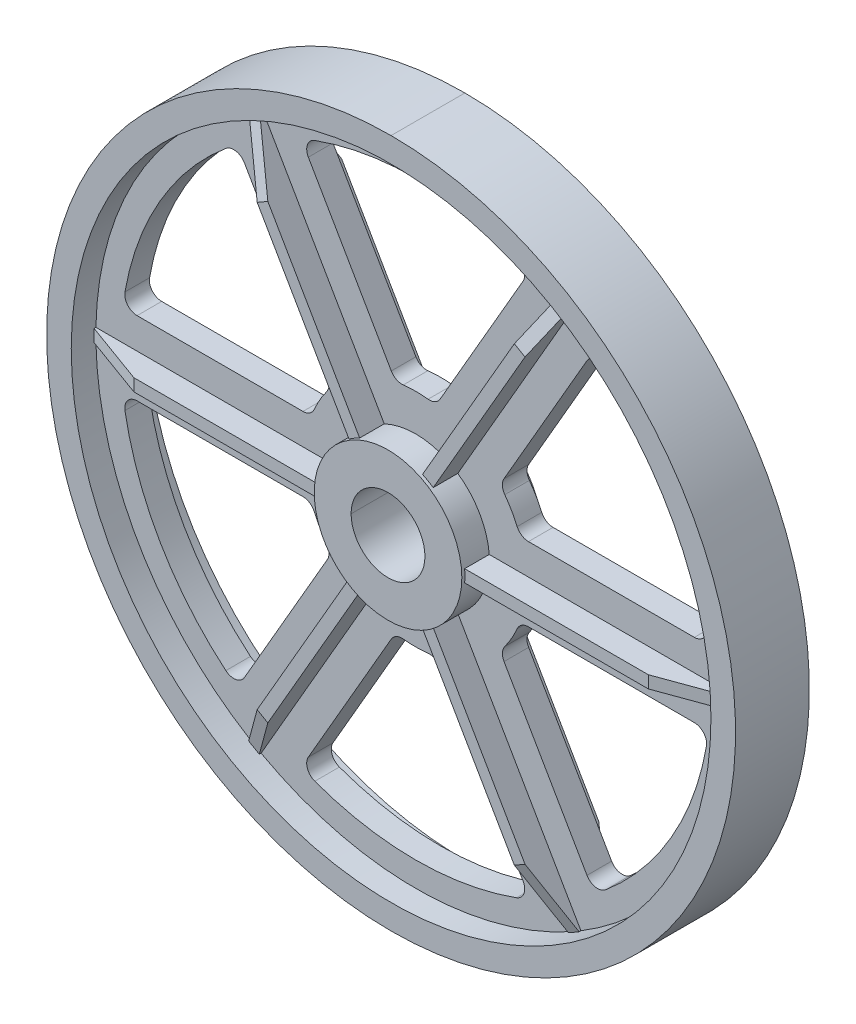
SolidWorks part; units mm, degrees
note: '?' marks a value the reader was unsure of.
extrude "CenterHub" add sketch "Sketch1" along normal mid plane 41.275
sketch "Sketch1" plane through (0, 0, 0) normal (0, 0, 1) x (1, 0, 0)
  circle A0 centre (0, 0) radius 38.1
  dimension "D1" = 76.2
revolve "Rim and Web" add sketch "Sketch2" angle 360 about L0
sketch "Sketch2" plane through (0, 0, 0) normal (1, 0, 0) x (0, 0, -1)
  line L0 (0, 0) -> (51.266, 0) construction
  line L1 (-6.35, 0) -> (6.35, 0)
  line L2 (-6.35, 0) -> (-6.35, 165.1)
  line L3 (-6.35, 165.1) -> (-19.05, 165.1)
  line L4 (6.35, 165.1) -> (6.35, 0)
  line L5 (-19.05, 177.8) -> (19.05, 177.8)
  line L6 (-19.05, 177.8) -> (-19.05, 165.1)
  line L7 (19.05, 165.1) -> (6.35, 165.1)
  line L8 (19.05, 165.1) -> (19.05, 177.8)
  line L9 (0, 0) -> (0, 95.9354) construction
  dimension "D1" = 355.6
  dimension "D2" = 12.7
  dimension "D3" = 38.1
  dimension "D4" = 12.7
ref_plane "Plane1" through (0, 0, 0) normal (0, 0, 1) x (1, 0, 0)
ref_plane "Plane2" through (0, 0, 0) normal (0, 1, 0) x (1, 0, 0)
ref_plane "Plane3" through (0, 0, 0) normal (1, 0, 0) x (0, 0, -1)
other "Configuration Table"
sketch "Sketch3" plane through (0, 0, 0) normal (0, 1, 0) x (1, 0, 0)
  line L0 (0, 0) -> (193.8767, 0) construction
  line L1 (0, -19.05) -> (132.747, -19.05)
  line L2 (132.747, -19.05) -> (167.64, -6.35)
  line L3 (165.1, -6.35) -> (-165.1, -6.35) construction
  line L4 (167.64, -6.35) -> (167.64, 6.35)
  line L5 (132.747, 19.05) -> (167.64, 6.35)
  line L6 (0, 19.05) -> (132.747, 19.05)
  line L7 (0, -19.05) -> (0, 19.05)
  line L8 (165.1, -19.05) -> (-165.1, -19.05) construction
  line L9 (165.1, -19.05) -> (165.1, -6.35) construction
  point P10 (167.64, 0)
  dimension "D1" = 20
  dimension "D2" = 2.54
extrude "Rib" add sketch "Sketch3" along normal mid plane 6.35
sketch "Sketch4" plane through (0, 0, 0) normal (0, 0, 1) x (1, 0, 0)
  line L0 (0, 0) -> (202.3803, 0) construction
  line L1 (0, 0) -> (96.4485, -167.0538) construction
  line L2 (92.1001, -121.4221) -> (43.4386, -37.1378)
  line L3 (151.2047, -19.05) -> (53.8815, -19.05)
  circle A1 centre (0, 0) radius 57.15
  arc A3 (43.4386, -37.1378) -> (53.8815, -19.05) centre (0, 0) ccw
  circle A4 centre (0, 0) radius 152.4
  arc A5 (92.1001, -121.4221) -> (151.2047, -19.05) centre (0, 0) ccw
  dimension "D1" = 19.05
  dimension "D2" = 19.05
  dimension "D5" = 60
  dimension "D3" = 19.05
  dimension "D4" = 12.7
extrude "Lightening hole" cut sketch "Sketch4" against normal through all and the other way through all
fillet "Fillet1" radius 6.35 4 edges at (151.2047, -19.05, 0) (92.1001, -121.4221, 0) (43.4386, -37.1378, 0) (53.8815, -19.05, 0)
pattern_circular "CirPattern1" count 6 every 60 about axis through (0, 0, 0) along (0, 0, 1) of "Lightening hole", "Fillet1", "Rib"
sketch "Sketch5" plane through (0, 0, 0) normal (0, 0, 1) x (1, 0, 0)
  circle A0 centre (0, 0) radius 19.05
  dimension "D1" = 38.1
extrude "Thru hole" cut sketch "Sketch5" against normal through all and the other way through all
sketch "Sketch6" plane through (0, 0, 20.6375) normal (0, 0, 1) x (1, 0, 0)
  line L3 (41.9093, 0) -> (-50.9157, 0)
split line "Split Line1"
sketch "Sketch7" plane through (0, 0, 0) normal (0, 1, 0) x (1, 0, 0)
  line L0 (0, 47.5496) -> (0, -42.3058)
  line L2 (0, 20.6375) -> (0, -20.6375) construction
split line "Split Line2"
ref_axis "Axis1" through (0, 0, 156.8576) along (0, 0, -1)?
equation "\"D2@CirPattern1\" = 360 / \"D1@CirPattern1\""
equation "\"D5@Sketch4\" = \"D2@CirPattern1\""
